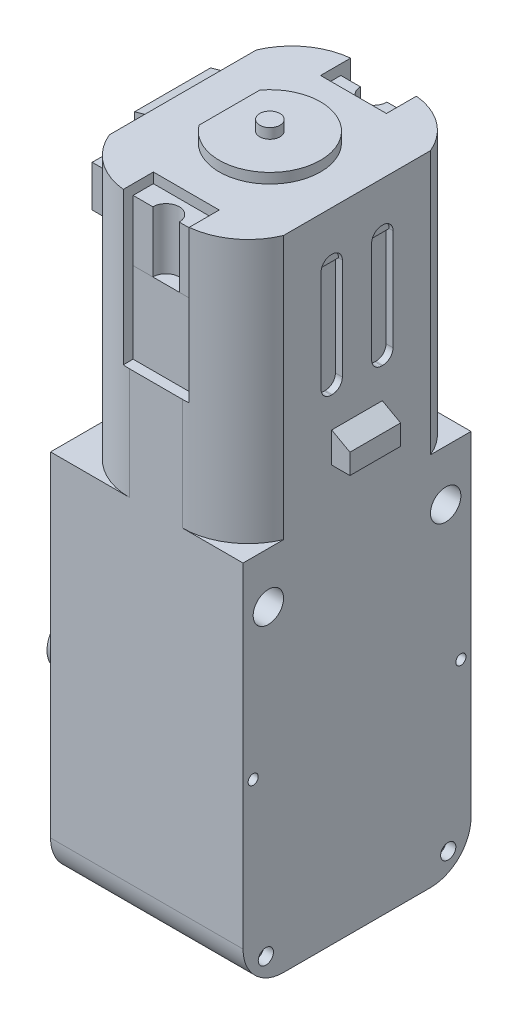
SolidWorks part; units mm, degrees
ref_plane "Alzado" through (0, 0, 0) normal (1, 0, 0) x (0, 1, 0)
ref_plane "Planta" through (0, 0, 0) normal (0, 0, 1) x (0, 1, 0)
ref_plane "Vista lateral" through (0, 0, 0) normal (0, 1, 0) x (-1, 0, 0)
sketch "Croquis1" plane through (0, 0, 0) normal (1, 0, 0) x (0, 1, 0)
  line L1 (-4.84, 11.25) -> (29.66, 11.25)
  line L2 (-7.34, 8.75) -> (-7.34, -8.75)
  line L3 (-4.84, -11.25) -> (29.66, -11.25)
  line L4 (29.66, 11.25) -> (29.66, -11.25)
  line L6 (5.66, 10.25) -> (-4.84, -8.75)
  line L8 (-4.84, 8.75) -> (5.66, -10.25)
  line L9 (-4.84, 0) -> (-0.0045, 0)
  arc A0 (-4.84, -11.25) -> (-7.34, -8.75) centre (-4.84, -8.75) cw
  arc A1 (-4.84, 11.25) -> (-7.34, 8.75) centre (-4.84, 8.75) ccw
  circle A2 centre (5.66, -10.25) radius 0.5
  circle A3 centre (5.66, 10.25) radius 0.5
  circle A4 centre (-0.0045, 0) radius 2.7322
  point P6 (-7.34, -11.25)
  point P9 (-7.34, 11.25)
  point P10 (-7.34, 0)
  dimension "D2" = 2.5
  dimension "D5" = 1
  dimension "D1" = 22.5
  dimension "D3" = 37
  dimension "D8" = 2.5
extrude "Saliente-Extruir2" add sketch "Croquis1" along normal blind 9.5 and the other way blind 9.5 contours L1 A1 L2 A0 L3 L4 A4 A2 A3 | A3 | L9 A4 L6 | L6 A4 L8 | L8 A4 L6 | L6 A4 L8 | L8 A4 L9 | A2 region at (0, 11.5559, 0) region at (0, 5.9069, -9.8315) region at (0, 1.4911, 0) region at (0, -0.0045, 1.745) region at (0, 5.4131, 10.6685) region at (0, -0.0045, -1.745) region at (0, -1.5001, 0.8823) region at (0, -1.5001, -0.8823)
sketch "Croquis2" plane through (0, 0, 0) normal (1, 0, 0) x (0, 1, 0)
  line L0 (-11.84, 3.2804) -> (-10.84, 3.2804)
  line L1 (-7.34, 8.75) -> (-7.34, -8.75) construction
  line L2 (-11.84, -2.5) -> (-11.84, 2.5)
  line L3 (-11.84, 0) -> (-13.0585, 0)
  line L4 (-11.84, -2.5) -> (-7.34, -2.5)
  line L5 (-11.84, -2.5) -> (-11.84, 2.5)
  line L6 (-11.84, 2.5) -> (-7.34, 2.5)
  line L7 (-7.34, -2.5) -> (-7.34, 2.5)
  line L8 (-11.84, -1.34) -> (-11.84, 1.34)
  line L10 (-12.4811, -2.5) -> (-12.4811, -1.5)
  line L11 (-12.4811, 2.5) -> (-12.4811, 1.5)
  circle A0 centre (-9.34, 0) radius 1.5
  dimension "D3" = 1
  dimension "D4" = 4.5
  dimension "D1" = 1
  dimension "D2" = 1
  dimension "D5" = 5
extrude "Saliente-Extruir4" add sketch "Croquis2" along normal blind 1.3 and the other way blind 1.3 contours L4 L7 L6 L5 L2 A0 region at (0, -11.7727, -1.92)
sketch "Croquis3" plane through (-9.5, 0, 0) normal (-1, 0, 0) x (0, -1, 0)
  circle A0 centre (0, 0) radius 2.5
extrude "Cortar-Extruir1" cut sketch "Croquis3" against normal blind 5
sketch "Croquis4" plane through (-9.5, 0, 0) normal (-1, 0, 0) x (0, 0, 1)
  line L0 (-12.6785, 24.66) -> (-12.6785, 5.66)
  line L2 (-11.25, 25.9631) -> (-10.25, 25.9631)
  line L3 (0, -7.34) -> (0, -15.1717)
  line L4 (8.75, -7.34) -> (-8.75, -7.34) construction
  line L5 (11.25, 25.9631) -> (10.25, 25.9631)
  line L6 (10.25, 25.9631) -> (10.25, 5.66)
  line L8 (-10.25, 4.4941) -> (-10.25, 25.9631)
  circle A0 centre (9.75, 5.66) radius 0.5
  circle A1 centre (8.75, -4.84) radius 0.75
  circle A2 centre (-9.75, 5.66) radius 0.5
  circle A3 centre (-8.75, -4.84) radius 0.75
  circle A4 centre (8.75, -4.84) radius 0.75
  circle A5 centre (9.75, 5.66) radius 0.5
  circle A6 centre (-9.75, 5.66) radius 0.5
  circle A7 centre (-8.75, -4.84) radius 0.75
  circle A8 centre (-8.75, -4.84) radius 0.75
  dimension "D3" = 1
  dimension "D4" = 1.5
  dimension "D1" = 19
  dimension "D2" = 1
sketch "Croquis5" plane through (9.5, 0, 0) normal (1, 0, 0) x (0, 1, 0)
  circle A0 centre (-4.84, 8.75) radius 0.75
  circle A1 centre (5.66, 9.75) radius 0.5
  circle A2 centre (5.66, -9.75) radius 0.5
  circle A3 centre (-4.84, -8.75) radius 0.75
extrude "Cortar-Extruir2" cut sketch "Croquis5" against normal blind 1
extrude "Cortar-Extruir3" cut sketch "Croquis4" against normal blind 1 contours A0 | A1 | A3 | A2 region at (-9.5, 5.66, 9.75) region at (-9.5, -4.84, 8.75) region at (-9.5, -4.84, -8.75)
sketch "Croquis6" plane through (-9.5, 0, 0) normal (-1, 0, 0) x (0, 0, 1)
  line L0 (13.1737, 24.66) -> (13.1737, 10.66)
  circle A0 centre (0, 10.66) radius 2
  dimension "D2" = 4
  dimension "D1" = 14
extrude "Saliente-Extruir6" add sketch "Croquis6" along normal blind 2 contours A0 region at (-9.5, 10.66, 0)
sketch "Croquis7" plane through (-9.5, 0, 0) normal (-1, 0, 0) x (0, 0, 1)
  line L0 (-11.25, 26.5829) -> (-10.25, 26.5829)
  line L1 (-12.8476, 24.66) -> (-12.8476, 19.66)
  line L2 (-10.25, 26.5829) -> (-10.25, 19.66)
  line L3 (-10.25, 19.66) -> (-12.8476, 19.66)
  line L4 (0, -11.84) -> (0, -18.0156)
  line L5 (-2.5, -11.84) -> (2.5, -11.84) construction
  line L7 (-7.25, 19.66) -> (-7.25, 21.16)
  line L8 (-7.25, 21.16) -> (-11.25, 21.16)
  circle A0 centre (-8.75, 19.66) radius 1.5
  circle A1 centre (8.75, 19.66) radius 1.5
  dimension "D1" = 1
  dimension "D2" = 5
  dimension "D3" = 1.5
  dimension "D4" = 4
extrude "Cortar-Extruir4" cut sketch "Croquis7" against normal through all contours A0 | A1 region at (-9.5, 19.66, -8.75)
sketch "Croquis8" plane through (0, 29.66, 0) normal (0, 1, 0) x (-1, 0, 0)
  line L1 (-3.5, 11.25) -> (1.7, 11.25)
  line L2 (-9.5, 7.25) -> (-9.5, -7.25)
  line L3 (-3.5, -11.25) -> (1.7, -11.25)
  line L4 (7.7, 7.25) -> (7.7, -7.25)
  line L5 (11.5, 0) -> (15.9145, 0)
  line L7 (11.5, -2) -> (11.5, 2) construction
  line L8 (0, 0) -> (0, 0.7272)
  arc A2 (7.7, 7.25) -> (1.7, 11.25) centre (1.7, 4.75) ccw
  arc A3 (7.7, -7.25) -> (1.7, -11.25) centre (1.7, -4.75) cw
  arc A5 (-3.5, 11.25) -> (-9.5, 7.25) centre (-3.5, 4.75) ccw
  arc A11 (-3.5, -11.25) -> (-9.5, -7.25) centre (-3.5, -4.75) cw
extrude "Saliente-Extruir7" add sketch "Croquis8" along normal blind 26 contours A11 A3 L4 A2 A5 region at (0.9, 29.66, 0)
sketch "Croquis9" plane through (-9.5, 0, 0) normal (-1, 0, 0) x (0, -1, 0)
  line L3 (-8.66, 15.3575) -> (-8.66, -16.1606) construction
  line L4 (-8.66, 15.3575) -> (18.8238, 15.3575)
  line L5 (-8.66, 15.3575) -> (-8.66, -16.1606)
  line L6 (-8.66, -16.1606) -> (18.8238, -16.1606)
  line L7 (18.8238, 15.3575) -> (18.8238, -16.1606)
extrude "Cortar-Extruir5" cut sketch "Croquis9" against normal through all
sketch "Croquis10" plane through (0, 8.66, 0) normal (0, -1, 0) x (-1, 0, 0)
  line L0 (9.5, -11.25) -> (9.5, 11.25) construction
  line L1 (9.5, -11.25) -> (-9.5, -11.25)
  line L2 (9.5, -11.25) -> (9.5, 11.25)
  line L3 (9.5, 11.25) -> (-9.5, 11.25)
  line L4 (-9.5, -11.25) -> (-9.5, 11.25)
  line L5 (0, 12.375) -> (0, -12.375) construction
  line L6 (-9.5, -11.25) -> (-9.5, -7.25) construction
  line L7 (-9.5, -11.25) -> (-9.5, 11.25) construction
  line L8 (9.5, -11.25) -> (1.7, -11.25) construction
  line L9 (9.5, -11.25) -> (-9.5, -11.25) construction
sketch "Croquis11" plane through (-9.5, 0, 0) normal (-1, 0, 0) x (0, 0, 1)
  line L1 (13.3634, 18.0947) -> (-15.0337, 18.0947)
  line L2 (13.3634, 18.0947) -> (13.3634, 2.7979)
  line L3 (13.3634, 2.7979) -> (-15.0337, 2.7979)
  line L4 (-15.0337, 18.0947) -> (-15.0337, 2.7979)
extrude "Cortar-Extruir7" cut sketch "Croquis11" against normal through all and the other way through all
sketch "Croquis12" plane through (-9.5, 0, 0) normal (-1, 0, 0) x (0, 0, 1)
  line L0 (-11.25, 29.66) -> (-11.25, 22.66)
  line L1 (-11.25, 18.0947) -> (-11.25, 29.66) construction
  line L3 (-11.25, 22.66) -> (12.1047, 22.66)
  line L4 (-11.25, 22.66) -> (-11.25, 15.491)
  line L5 (-11.25, 15.491) -> (12.1047, 15.491)
  line L6 (12.1047, 22.66) -> (12.1047, 15.491)
  line M2 (-11.25, 29.66) -> (-11.25, 18.0947)
  line M3 (-11.25, 18.0947) -> (11.25, 18.0947)
  line M4 (11.25, 18.0947) -> (11.25, 29.66)
  circle M6 centre (8.75, 19.66) radius 1.5
  circle M7 centre (-8.75, 19.66) radius 1.5
  dimension "D1" = 7
extrude "Cortar-Extruir8" cut sketch "Croquis12" against normal through all contours L3 M2 M3 M4 M6 M7 | L6 L3 L4 L5 M4 M3 region at (-9.5, 20.4918, 0) region at (-9.5, 17.009, 1.1057)
sketch "Croquis14" plane through (0, 22.66, 0) normal (0, -1, 0) x (-1, 0, 0)
  line L1 (9.5, -11.25) -> (-9.5, -11.25)
  line L2 (9.5, -11.25) -> (9.5, 11.25)
  line L3 (9.5, 11.25) -> (-9.5, 11.25)
  line L4 (-9.5, -11.25) -> (-9.5, 11.25)
extrude "Saliente-Extruir9" add sketch "Croquis14" along normal blind 30
sketch "Croquis15" plane through (-9.5, 0, 0) normal (-1, 0, 0) x (0, 0, 1)
  line L0 (0, -7.34) -> (0, -12.8155)
  line L1 (11.25, -7.34) -> (-11.25, -7.34) construction
  line L2 (-11.25, 29.66) -> (-10.25, 29.66)
  line L3 (-7.25, 29.66) -> (-11.25, 29.66) construction
  line L4 (-11.25, 29.66) -> (-11.25, 24.66)
  line L5 (-11.25, -7.34) -> (-11.25, 29.66) construction
  line L6 (-11.25, 24.66) -> (-10.25, 24.66)
  line L7 (-10.25, 24.66) -> (-10.25, 29.66)
  circle A0 centre (-8.75, 24.66) radius 1.5
  circle A1 centre (8.75, 24.66) radius 1.5
  dimension "D3" = 3
  dimension "D1" = 5
  dimension "D2" = 1
extrude "Cortar-Extruir9" cut sketch "Croquis15" against normal through all contours A1 | A0 region at (-9.5, 24.66, -8.75) region at (-9.5, 24.66, 8.75)
sketch "Croquis16" plane through (-9.5, 0, 0) normal (-1, 0, 0) x (0, 0, 1)
  line L0 (11.25, 29.66) -> (11.25, 15.66)
  line L1 (11.25, -7.34) -> (11.25, 29.66) construction
  circle A0 centre (0, 15.66) radius 2
  dimension "D2" = 4
  dimension "D1" = 14
extrude "Saliente-Extruir10" add sketch "Croquis16" along normal blind 2 contours A0 region at (-9.5, 15.66, 0)
sketch "Croquis17" plane through (-9.5, 0, 0) normal (-1, 0, 0) x (0, 0, 1)
  line L0 (11.25, 29.66) -> (11.25, 10.66)
  line L1 (11.25, -7.34) -> (11.25, 29.66) construction
  line L2 (11.25, 10.66) -> (10.75, 10.66)
  line L3 (11.25, -7.34) -> (-11.25, -7.34) construction
  line L4 (14.7504, -3.34) -> (14.7504, -7.34)
  line L5 (9.75, 10.66) -> (9.75, -12.757)
  line L6 (11.25, -3.34) -> (-13.714, -3.34)
  line L7 (11.25, -7.34) -> (7.25, -3.34)
  line L8 (0, -7.34) -> (0, -17.085)
  line L9 (-11.25, -3.34) -> (-11.25, -7.34)
  line L10 (-11.25, -7.34) -> (-7.25, -7.34)
  line L11 (-7.25, -7.34) -> (7.25, -7.34)
  line L12 (7.25, -7.34) -> (11.25, -7.34)
  line L13 (11.25, -3.34) -> (11.25, -7.34)
  line L14 (11.25, -7.34) -> (7.25, -7.34)
  line L15 (11.25, -3.34) -> (11.25, -7.34)
  circle A0 centre (10.25, 10.66) radius 0.5
  arc A1 (7.25, -7.34) -> (9.75, -0.2175) centre (7.25, -3.34) ccw
  circle A4 centre (9, -5.09) radius 0.75
  circle A5 centre (-9, -5.09) radius 0.75
  arc A6 (-7.25, -7.34) -> (-11.25, -3.34) centre (-7.25, -3.34) cw
  circle A7 centre (-10.25, 10.66) radius 0.5
  arc A8 (7.25, -7.34) -> (11.25, -3.34) centre (7.25, -3.34) ccw
  dimension "D3" = 1
  dimension "D4" = 8
  dimension "D5" = 1.5
  dimension "D1" = 19
  dimension "D2" = 0.5
sketch "Croquis18" plane through (-9.5, 0, 0) normal (-1, 0, 0) x (0, 0, 1)
extrude "Cortar-Extruir10" cut sketch "Croquis17" against normal through all contours A0 | A4 L7 | L7 A4 | A7 | A5 region at (-9.5, 10.66, 10.25) region at (-9.5, -4.8649, 9.2251) region at (-9.5, -5.3151, 8.7749) region at (-9.5, 10.66, -10.25)
sketch "Croquis19" plane through (-9.5, 0, 0) normal (-1, 0, 0) x (0, 0, 1)
  line L0 (11.25, -7.34) -> (11.25, -3.34)
  line L1 (11.25, -7.34) -> (11.25, 29.66) construction
  line L2 (0, -7.34) -> (0, -13.8514)
  line L3 (11.25, -7.34) -> (7.25, -7.34)
  line L4 (11.25, -7.34) -> (-11.25, -7.34) construction
  line L5 (-11.25, -7.34) -> (-7.25, -7.34)
  line L6 (-11.25, -7.34) -> (-11.25, -3.34)
  arc A0 (7.25, -7.34) -> (11.25, -3.34) centre (7.25, -3.34) ccw
  arc A1 (-7.25, -7.34) -> (-11.25, -3.34) centre (-7.25, -3.34) cw
  line M9 (-11.25, 29.66) -> (-11.25, -7.34)
  line M10 (-11.25, -7.34) -> (11.25, -7.34)
  line M11 (11.25, -7.34) -> (11.25, 29.66)
  dimension "D1" = 8
sketch "Croquis20" plane through (0, -7.34, 0) normal (0, -1, 0) x (1, 0, 0)
  line L5 (-8.6868, 10.6536) -> (8.5298, 10.6536)
  line L6 (-8.6868, 10.6536) -> (-8.6868, -10.8334)
  line L7 (-8.6868, -10.8334) -> (8.5298, -10.8334)
  line L8 (8.5298, 10.6536) -> (8.5298, -10.8334)
  line L9 (2.0429, 4.3316) -> (2.816, 4.3316)
  line L10 (2.0429, 4.3316) -> (2.0429, 4.8022)
  line L11 (2.0429, 4.8022) -> (2.816, 4.8022)
  line L12 (2.816, 4.3316) -> (2.816, 4.8022)
extrude "Saliente-Extruir12" add sketch "Croquis20" against normal blind 24 contours L10 L9 L12 L11
sketch "Croquis21" plane through (0, -7.34, 0) normal (0, -1, 0) x (-1, 0, 0)
  line L0 (9.5, -11.25) -> (-9.5, -11.25) construction
  line L1 (8.3272, -11.25) -> (-8.5298, -11.25)
  line L2 (8.3272, -11.25) -> (8.3272, 11.25)
  line L3 (8.3272, 11.25) -> (-8.5298, 11.25)
  line L4 (-8.5298, -11.25) -> (-8.5298, 11.25)
  line L5 (9.5, 11.25) -> (-9.5, 11.25) construction
extrude "Saliente-Extruir13" add sketch "Croquis21" against normal blind 24
extrude "Cortar-Extruir11" cut sketch "Croquis19" against normal through all contours A0 M10 M11 | A1 M10 M9 region at (-9.5, -6.4465, 10.3565) region at (-9.5, -6.4465, -10.3565)
sketch "Croquis22" plane through (-9.5, 0, 0) normal (-1, 0, 0) x (0, 0, 1)
  line L0 (7.25, -7.34) -> (17.3359, -7.34)
  line L1 (11.25, -7.34) -> (11.25, 3.86)
  line L2 (11.25, -3.34) -> (11.25, 29.66) construction
  line L3 (11.25, 3.86) -> (-11.25, 3.86)
  line L4 (-11.25, -3.34) -> (-11.25, 29.66) construction
  circle A0 centre (0, 3.86) radius 2.6
  dimension "D2" = 5.2
  dimension "D1" = 11.2
extrude "Cortar-Extruir12" cut sketch "Croquis22" against normal blind 5 contours L3 A0 | L3 A0 region at (-9.5, 2.7565, 0) region at (-9.5, 4.9635, 0)
sketch "Croquis23" plane through (-9.5, 0, 0) normal (-1, 0, 0) x (0, 0, 1)
  circle A0 centre (0, 3.86) radius 2.6
  circle A1 centre (0, 3.86) radius 2.75
  dimension "D1" = 5.5
extrude "Saliente-Extruir14" add sketch "Croquis23" along normal blind 0.5 draft 8 contours A1 | A0
sketch "Croquis24" plane through (0, -7.34, 0) normal (0, -1, 0) x (1, 0, 0)
  line L1 (-1.25, -2.5) -> (1.25, -2.5)
  line L2 (-1.25, -2.5) -> (-1.25, 2.5)
  line L3 (-1.25, 2.5) -> (1.25, 2.5)
  line L4 (1.25, -2.5) -> (1.25, 2.5)
  line L5 (-1.25, -2.5) -> (1.25, 2.5) construction
  line L6 (-1.25, 2.5) -> (1.25, -2.5) construction
  point P0 (0, 0)
  dimension "D1" = 2.5
  dimension "D2" = 5
extrude "Saliente-Extruir15" add sketch "Croquis24" along normal blind 4.7
sketch "Croquis25" plane through (-1.25, 0, 0) normal (-1, 0, 0) x (0, 0, 1)
  line L0 (2.5, -12.04) -> (-2.5, -12.04) construction
  circle A0 centre (0, -9.64) radius 1.4
  dimension "D1" = 2.8
  dimension "D2" = 2.4
extrude "Cortar-Extruir13" cut sketch "Croquis25" against normal blind 4.7
sketch "Croquis26" plane through (-7.7, 0, 0) normal (-1, 0, 0) x (0, -1, 0)
  line L0 (-29.66, -7.25) -> (-33.66, -7.25)
  line L1 (-55.66, -7.25) -> (-29.66, -7.25) construction
  line L2 (-33.66, -7.25) -> (-33.66, 7.25)
  line L3 (-55.66, 7.25) -> (-29.66, 7.25) construction
  line L5 (-36.66, 2.5) -> (-33.66, 2.5)
  line L6 (-36.66, 2.5) -> (-36.66, -2.5)
  line L7 (-36.66, -2.5) -> (-33.66, -2.5)
  line L8 (-33.66, 2.5) -> (-33.66, -2.5)
  line L9 (-36.66, 2.5) -> (-33.66, -2.5) construction
  line L10 (-36.66, -2.5) -> (-33.66, 2.5) construction
  point P5 (-35.16, 0)
  point P14 (-33.66, 0)
  dimension "D1" = 4
  dimension "D2" = 3
  dimension "D3" = 5
extrude "Saliente-Extruir17" add sketch "Croquis26" along normal blind 2 and the other way blind 19 contours L6 L7 L2 L5 region at (-7.7, 35.16, 0)
sketch "Croquis27" plane through (0, 0, 0) normal (0, 0, 1) x (0, 1, 0)
  line L0 (33.66, 9.7) -> (35.66, 9.7)
  line L1 (36.66, 9.7) -> (33.66, 9.7) construction
  line L2 (35.66, 9.7) -> (35.66, -11.3)
  line L3 (36.66, -11.3) -> (33.66, -11.3) construction
  line L4 (35.66, 9.7) -> (36.66, 7.7)
  line L5 (36.66, 7.7) -> (36.66, 9.7)
  line L6 (36.66, 9.7) -> (35.66, 9.7)
  line L7 (35.66, -11.3) -> (36.66, -9.5)
  line L8 (36.66, -9.5) -> (36.66, -11.3)
  line L9 (36.66, -11.3) -> (35.66, -11.3)
  dimension "D1" = 2
extrude "Cortar-Extruir14" cut sketch "Croquis27" against normal through all and the other way through all contours L5 L6 L4 | L9 L8 L7 region at (10.7, 36.3267, 0) region at (-9.0333, 36.3267, 0)
sketch "Croquis28" plane through (-7.7, 0, 0) normal (-1, 0, 0) x (0, -1, 0)
  line L0 (-36.66, -2.5) -> (-39.66, -2.5)
  line L1 (-36.66, 0) -> (-38.0942, 0)
  line L2 (-45.66, -1.4465) -> (-40.66, -1.4465)
  line L3 (-46.66, -2.4465) -> (-46.66, -2.5535)
  line L4 (-45.66, -3.5535) -> (-40.66, -3.5535)
  line L5 (-39.66, -2.4465) -> (-39.66, -2.5535)
  line L6 (-46.66, -1.4465) -> (-39.66, -3.5535) construction
  line L7 (-46.66, -3.5535) -> (-39.66, -1.4465) construction
  line L8 (-36.66, 2.5) -> (-36.66, -2.5) construction
  line L9 (-45.66, 3.5535) -> (-40.66, 3.5535)
  line L10 (-39.66, 2.4465) -> (-39.66, 2.5535)
  line L11 (-45.66, 1.4465) -> (-40.66, 1.4465)
  line L12 (-46.66, 2.4465) -> (-46.66, 2.5535)
  arc A0 (-45.66, -3.5535) -> (-46.66, -2.5535) centre (-45.66, -2.5535) cw
  arc A1 (-46.66, -2.4465) -> (-45.66, -1.4465) centre (-45.66, -2.4465) cw
  arc A2 (-39.66, -2.5535) -> (-40.66, -3.5535) centre (-40.66, -2.5535) cw
  arc A3 (-39.66, -2.4465) -> (-40.66, -1.4465) centre (-40.66, -2.4465) ccw
  arc A4 (-39.66, 2.5535) -> (-40.66, 3.5535) centre (-40.66, 2.5535) ccw
  arc A5 (-39.66, 2.4465) -> (-40.66, 1.4465) centre (-40.66, 2.4465) cw
  arc A6 (-45.66, 3.5535) -> (-46.66, 2.5535) centre (-45.66, 2.5535) ccw
  arc A7 (-46.66, 2.4465) -> (-45.66, 1.4465) centre (-45.66, 2.4465) ccw
  point P2 (-43.16, -2.5)
  dimension "D3" = 1
  dimension "D1" = 3
  dimension "D2" = 7
extrude "Cortar-Extruir15" cut sketch "Croquis28" against normal through all contours L12 A7 L11 A5 L10 A4 L9 A6 | L2 A3 L5 A2 L4 A0 L3 A1 region at (-7.7, 43.16, 2.5)
sketch "Croquis29" plane through (9.5, 0, 0) normal (1, 0, 0) x (0, 1, 0)
  line L0 (40.66, -1.4465) -> (45.66, -1.4465) construction
  line L5 (36.66, 0) -> (38.1303, 0)
  line L6 (36.66, -2.5) -> (36.66, 2.5) construction
  line L7 (40.66, -3.5535) -> (45.66, -3.5535) construction
  line L8 (40.66, -1.4465) -> (50.66, -1.4465)
  line L13 (40.66, -1.4465) -> (40.66, -3.5535)
  line L14 (40.66, -3.5535) -> (50.66, -3.5535)
  line L15 (51.66, -2.4465) -> (51.66, -2.5535)
  line L16 (40.66, 3.5535) -> (50.66, 3.5535)
  line L17 (51.66, 2.4465) -> (51.66, 2.5535)
  line L18 (40.66, 1.4465) -> (50.66, 1.4465)
  line L19 (40.66, 1.4465) -> (40.66, 3.5535)
  arc A1 (51.8241, -1.5254) -> (51.8281, -1.6145) centre (52.8241, -1.5254) ccw
  arc A2 (51.66, -2.5535) -> (50.66, -3.5535) centre (50.66, -2.5535) cw
  arc A3 (51.66, -2.4465) -> (50.66, -1.4465) centre (50.66, -2.4465) ccw
  arc A4 (51.66, 2.5535) -> (50.66, 3.5535) centre (50.66, 2.5535) ccw
  arc A5 (51.66, 2.4465) -> (50.66, 1.4465) centre (50.66, 2.4465) cw
  point P16 (52.66, -3.4465)
  point P19 (51.66, -3.5535)
  point P24 (39.66, -1.4465)
  arc M37 (45.66, -1.4465) -> (46.66, -2.4465) centre (45.66, -2.4465) cw
  line M38 (46.66, -2.4465) -> (46.66, -2.5535)
  arc M39 (46.66, -2.5535) -> (45.66, -3.5535) centre (45.66, -2.5535) cw
  arc M44 (45.66, 3.5535) -> (46.66, 2.5535) centre (45.66, 2.5535) cw
  line M45 (46.66, 2.5535) -> (46.66, 2.4465)
  arc M46 (46.66, 2.4465) -> (45.66, 1.4465) centre (45.66, 2.4465) cw
  dimension "D2" = 1
  dimension "D1" = 11
extrude "Cortar-Extruir16" cut sketch "Croquis29" against normal blind 7 contours A5 L17 A4 L16 L18 M44 M45 M46 | L15 A3 L8 L14 A2 M37 M38 M39 region at (9.5, 48.9563, -2.5) region at (9.5, 48.9563, 2.5)
sketch "Croquis30" plane through (0, 0, 0) normal (0, 0, 1) x (0, 1, 0)
  line L0 (55.66, 8.7) -> (48.16, 8.7)
  line L1 (55.66, 8.7) -> (55.66, 7.7)
  line L2 (55.66, 7.7) -> (55.66, 6.2)
  line L3 (55.66, 1.7) -> (55.66, 7.7) construction
  line L4 (55.66, 8.7) -> (55.66, 9.8676)
  line L5 (48.16, 8.7) -> (55.66, 8.7)
  line L6 (48.16, 8.7) -> (48.16, 7.7)
  line L7 (48.16, 7.7) -> (55.66, 7.7)
  line L8 (55.66, 8.7) -> (55.66, 7.7)
  line L9 (55.66, 9.8676) -> (54.66, 9.8676)
  line L10 (48.16, 8.7) -> (48.16, 10.3949)
  line L11 (48.16, 10.3949) -> (49.16, 10.3949)
  line L12 (49.16, 10.3949) -> (49.16, 7.7)
  line L13 (54.66, 9.8676) -> (54.66, 7.7)
  dimension "D1" = 7.5
  dimension "D2" = 1.5
  dimension "D3" = 1
  dimension "D4" = 1
  dimension "D5" = 1
extrude "Saliente-Extruir18" add sketch "Croquis30" along normal blind 3.75 and the other way blind 3.75 contours L6 L5 L8 L7
sketch "Croquis31" plane through (0, 0, 0) normal (0, 0, 1) x (0, 1, 0)
  line L0 (55.66, 8.7) -> (55.66, 9.5141)
  line L1 (55.66, 9.5141) -> (54.66, 9.5141)
  line L2 (48.16, 8.9893) -> (49.16, 8.9893)
  line L3 (49.16, 8.9893) -> (49.16, 7.7)
  line L4 (55.66, 7.7) -> (29.66, 7.7) construction
  line L5 (49.16, 7.7) -> (54.66, 7.7)
  line L7 (49.16, 7.7) -> (54.66, 7.7)
  line L8 (49.16, 7.7) -> (49.16, 6.2)
  line L9 (49.16, 6.2) -> (54.66, 6.2)
  line L10 (54.66, 7.7) -> (54.66, 6.2)
  dimension "D1" = 1
  dimension "D2" = 1
  dimension "D3" = 1.5
extrude "Cortar-Extruir17" cut sketch "Croquis31" against normal through all and the other way through all contours L10 L5 L8 L9 region at (-6.95, 51.91, 0)
sketch "Croquis32" plane through (0, 0, 0) normal (0, 0, 1) x (0, 1, 0)
  line L0 (48.16, 7.7) -> (48.16, 8.7)
  line L1 (48.16, 8.7) -> (48.926, 8.7)
  line L2 (48.16, 8.7) -> (55.66, 8.7) construction
  line L3 (48.926, 8.7) -> (48.16, 7.7)
extrude "Cortar-Extruir18" cut sketch "Croquis32" against normal through all and the other way through all
sketch "Croquis33" plane through (0, 0, 3.75) normal (0, 0, 1) x (1, 0, 0)
  line L0 (-7.7, 55.66) -> (-8.7, 55.3867)
  line L1 (-8.7, 48.926) -> (-8.7, 55.66) construction
  line L2 (-8.7, 55.3867) -> (-7.7, 55.3867)
  line L3 (-7.7, 55.66) -> (-7.7, 54.66) construction
  line L4 (-7.7, 55.3867) -> (-7.7, 55.66)
  line L5 (-8.7, 55.3867) -> (-8.7, 55.66)
  line L6 (-8.7, 55.66) -> (-7.7, 55.66)
  line L7 (-8.7, 55.3867) -> (-8.7, 55.66)
  line M4 (-8.7, 55.66) -> (-8.7, 48.926)
  line M9 (-7.7, 55.66) -> (-8.7, 55.66)
extrude "Cortar-Extruir22" cut sketch "Croquis33" against normal through all and the other way through all contours L0 M9 M4 region at (-8.3667, 55.5689, 3.75)
sketch "Croquis34" plane through (0, 55.66, 0) normal (0, 1, 0) x (1, 0, 0)
  line L5 (3.5, -11.25) -> (-1.7, -11.25)
  line L6 (0.9, -11.25) -> (0.9, -13.2757)
  line L7 (12.6416, 0) -> (17.759, 0)
  line L8 (4.15, -8.25) -> (-2.35, -8.25)
  line L9 (4.15, -8.25) -> (4.15, -11.25)
  line L10 (4.15, -11.25) -> (-2.35, -11.25)
  line L11 (-2.35, -8.25) -> (-2.35, -11.25)
  line L12 (4.15, -8.25) -> (-2.35, -11.25) construction
  line L13 (4.15, -11.25) -> (-2.35, -8.25) construction
  line L14 (4.15, 11.25) -> (-2.35, 11.25)
  line L15 (-2.35, 8.25) -> (-2.35, 11.25)
  line L16 (4.15, 8.25) -> (-2.35, 8.25)
  line L17 (4.15, 8.25) -> (4.15, 11.25)
  point P4 (0.9, -9.75)
  arc M9 (-7.7, -7.25) -> (-1.7, -11.25) centre (-1.7, -4.75) ccw
  line M10 (-1.7, -11.25) -> (3.5, -11.25)
  arc M11 (3.5, -11.25) -> (9.5, -7.25) centre (3.5, -4.75) ccw
  arc M13 (9.5, 7.25) -> (3.5, 11.25) centre (3.5, 4.75) ccw
  line M14 (3.5, 11.25) -> (-1.7, 11.25)
  arc M15 (-1.7, 11.25) -> (-7.7, 7.25) centre (-1.7, 4.75) ccw
  dimension "D1" = 6.5
  dimension "D2" = 3
extrude "Cortar-Extruir23" cut sketch "Croquis34" against normal blind 15 contours L8 L11 L5 L9 M9 M10 M11 | L16 L17 L15 M13 M14 M15 region at (0.9, 55.66, 9.7489) region at (0.9, 55.66, -9.7489)
sketch "Croquis35" plane through (0, 55.66, 0) normal (0, 1, 0) x (-1, 0, 0)
  line L0 (-9.5, 0) -> (3.1, 0)
  line L1 (-9.5, 11.25) -> (-9.5, -11.25) construction
  line L2 (7.7, -3.75) -> (7.7, 3.75) construction
  line L3 (-9.5, 7.25) -> (7.7, 7.25)
  line L4 (-5.9, 0) -> (3.1, 0)
  line L5 (3.1, 0) -> (3.1, 3)
  line L6 (3.1, 3) -> (3.1, -3)
  line L7 (4.1, 0) -> (7.7, 0)
  arc A0 (3.1, 3) -> (3.1, -3) centre (-0.9, 0) ccw
  dimension "D1" = 10
  dimension "D2" = 9
extrude "Cortar-Extruir24" cut sketch "Croquis35" against normal blind 5 contours L5 A0 L0 | L0 A0 L6 region at (1.1418, 55.66, 2.1759) region at (1.1418, 55.66, -2.1759)
sketch "Croquis37" plane through (0, 39.66, 0) normal (0, 1, 0) x (1, 0, 0)
  line L5 (8.8118, -6.8201) -> (-6.9662, -6.8201)
  line L6 (8.8118, -6.8201) -> (8.8118, 7.9883)
  line L7 (8.8118, 7.9883) -> (-6.9662, 7.9883)
  line L8 (-6.9662, -6.8201) -> (-6.9662, 7.9883)
extrude "Saliente-Extruir19" add sketch "Croquis37" along normal blind 11 separate body
sketch "Croquis38" plane through (-6.2, 0, 0) normal (-1, 0, 0) x (0, 0, 1)
  line L0 (-9.4404, 54.66) -> (-9.4404, 49.16) construction
  line L1 (9.4404, 54.66) -> (-9.4404, 54.66)
  line L2 (9.4404, 54.66) -> (9.4404, 50.5786)
  line L3 (9.4404, 50.5786) -> (-9.4404, 50.5786)
  line L4 (-9.4404, 54.66) -> (-9.4404, 50.5786)
extrude "Saliente-Extruir21" add sketch "Croquis38" along normal blind 1 separate body
sketch "Croquis39" plane through (-7.2, 0, 0) normal (-1, 0, 0) x (0, 0, 1)
  line L0 (3.75, 54.66) -> (7.25, 54.66) construction
  line L1 (4.5442, 54.66) -> (-4.5793, 54.66)
  line L2 (4.5442, 54.66) -> (4.5442, 50.5786)
  line L3 (4.5442, 50.5786) -> (-4.5793, 50.5786)
  line L4 (-4.5793, 54.66) -> (-4.5793, 50.5786)
  line L5 (-9.4404, 50.5786) -> (9.4404, 50.5786) construction
extrude "Saliente-Extruir23" add sketch "Croquis39" along normal blind 0.6 separate body
sketch "Croquis40" plane through (0, 40.66, 0) normal (0, 1, 0) x (-1, 0, 0)
  line L0 (2.35, -8.25) -> (2.35, -11.2174) construction
  line L1 (-4.15, -8.25) -> (2.35, -8.25)
  line L2 (-4.15, -8.25) -> (-4.15, -10.25)
  line L3 (-4.15, -10.25) -> (2.35, -10.25)
  line L4 (2.35, -8.25) -> (2.35, -10.25)
  line L5 (-11.3, 0) -> (-17.9203, 0)
  line L6 (-11.3, 2.5) -> (-11.3, -2.5) construction
  line L7 (-4.15, 10.25) -> (2.35, 10.25)
  line L8 (2.35, 8.25) -> (2.35, 10.25)
  line L9 (-4.15, 8.25) -> (2.35, 8.25)
  line L10 (-4.15, 8.25) -> (-4.15, 10.25)
  line M10 (2.35, -8.25) -> (-4.15, -8.25)
  line M11 (-4.15, -8.25) -> (-4.15, -11.2174)
  line M15 (2.35, -11.2174) -> (2.35, -8.25)
  dimension "D1" = 2
extrude "Saliente-Extruir24" add sketch "Croquis40" along normal blind 8 separate body contours L10 L9 L8 L7 | L3 M11 M15 M10 region at (0.9, 40.66, -9.25) region at (0.9, 40.66, 9.25)
sketch "Croquis41" plane through (0, 50.66, 0) normal (0, 1, 0) x (1, 0, 0)
  circle A0 centre (0.9, 0) radius 1
  dimension "D1" = 2
extrude "Saliente-Extruir26" add sketch "Croquis41" along normal blind 7 separate body contours A0
sketch "Croquis42" plane through (0, 48.66, 0) normal (0, 1, 0) x (1, 0, 0)
  line L0 (4.15, -10.25) -> (-2.35, -10.25) construction
  line L1 (-2.35, -8.25) -> (4.15, -8.25)
  line L2 (-2.35, -8.25) -> (-2.35, -10.25)
  line L3 (-2.35, -10.25) -> (-0.4059, -10.25)
  line L4 (4.15, -8.25) -> (4.15, -10.25)
  line L5 (2.2059, -10.25) -> (4.15, -10.25)
  line L6 (-11.5, 0) -> (-14.0238, 0)
  line L7 (-11.5, 2) -> (-11.5, -2) construction
  line L8 (2.2059, 10.25) -> (4.15, 10.25)
  line L9 (4.15, 8.25) -> (4.15, 10.25)
  line L10 (-2.35, 8.25) -> (4.15, 8.25)
  line L11 (-2.35, 8.25) -> (-2.35, 10.25)
  line L12 (-2.35, 10.25) -> (-0.4059, 10.25)
  arc A0 (2.2059, -10.25) -> (-0.4059, -10.25) centre (0.9, -10.25) ccw
  arc A1 (2.2059, 10.25) -> (-0.4059, 10.25) centre (0.9, 10.25) cw
  line M8 (4.15, -10.25) -> (4.15, -8.25)
  line M9 (4.15, -8.25) -> (-2.35, -8.25)
  line M10 (-2.35, -8.25) -> (-2.35, -10.25)
  line M11 (-2.35, -10.25) -> (4.15, -10.25)
extrude "Saliente-Extruir27" add sketch "Croquis42" along normal blind 6 separate body contours A0 M11 M8 M9 M10 | L8 A1 L12 L11 L10 L9 region at (0.9, 48.66, 8.318) region at (3.1779, 48.66, -10.182)
sketch "Croquis43" plane through (0, 50.66, 0) normal (0, 1, 0) x (1, 0, 0)
  line L0 (-3.1, -3) -> (-3.1, 3)
  arc A0 (-3.1, -3) -> (-3.1, 3) centre (0.9, 0) ccw
extrude "Saliente-Extruir28" add sketch "Croquis43" along normal blind 6 separate body contours A0 L0
sketch "Croquis44" plane through (0, 50.66, 0) normal (0, 1, 0) x (1, 0, 0)
  line L1 (9.1152, -4.8548) -> (3.9007, -4.8548)
  line L2 (9.1152, -4.8548) -> (9.1152, 4.72)
  line L3 (9.1152, 4.72) -> (3.9007, 4.72)
  line L4 (3.9007, -4.8548) -> (3.9007, 4.72)
extrude "Saliente-Extruir29" add sketch "Croquis44" along normal blind 2 separate body
sketch "Croquis46" plane through (-7.2, 0, 0) normal (-1, 0, 0) x (0, 0, 1)
  line L0 (4.5442, 50.5786) -> (4.5442, 54.66) construction
  line L4 (8.1975, 52.779) -> (8.1975, 52.4596)
  line L5 (0, 57.66) -> (0, 63.4537)
  line L6 (1, 57.66) -> (-1, 57.66) construction
  line L7 (-8.1975, 52.779) -> (-8.1975, 52.4596)
  line L12 (-4.5442, 53.779) -> (-7.1975, 53.779)
  line L13 (-4.5442, 51.4596) -> (-4.5442, 53.779)
  line L14 (4.5442, 51.4596) -> (7.1975, 51.4596)
  line L15 (4.5442, 51.4596) -> (4.5442, 53.779)
  line L16 (4.5442, 53.779) -> (7.1975, 53.779)
  line L17 (8.1975, 51.4596) -> (8.1975, 53.779)
  line L18 (-4.5442, 51.4596) -> (-7.1975, 51.4596)
  arc A0 (7.1975, 51.4596) -> (8.1975, 52.4596) centre (7.1975, 52.4596) ccw
  arc A1 (7.1975, 53.779) -> (8.1975, 52.779) centre (7.1975, 52.779) cw
  circle A2 centre (7.1975, 52.6193) radius 0.6976
  circle A3 centre (-7.1975, 52.6193) radius 0.6976
  arc A4 (-7.1975, 51.4596) -> (-8.1975, 52.4596) centre (-7.1975, 52.4596) cw
  arc A5 (-7.1975, 53.779) -> (-8.1975, 52.779) centre (-7.1975, 52.779) ccw
  point P0 (4.5442, 52.6193)
  point P9 (4.5442, 53.779)
  dimension "D1" = 1
extrude "Saliente-Extruir32" add sketch "Croquis46" along normal blind 0.4 separate body contours A1 L16 L15 L14 A0 L4 A2 | L12 A5 L7 A4 L18 L13 A3 region at (-7.2, 52.6193, 6.0712) region at (-7.2, 52.6193, -6.0712)
sketch "Croquis47" plane through (-4.5, 0, 0) normal (-1, 0, 0) x (0, 0, 1)
  circle A0 centre (0, 3.86) radius 2.6
  dimension "D1" = 5.2
extrude "Saliente-Extruir33" add sketch "Croquis47" along normal blind 14 separate body
sketch "Croquis48" plane through (-18.5, 0, 0) normal (-1, 0, 0) x (0, 0, 1)
  line L0 (0, 5.61) -> (2.9802, 5.61)
  line L1 (2.9802, 5.61) -> (-2.9064, 5.61)
  line L2 (-2.9064, 5.61) -> (0, 2.11)
  line L3 (0, 2.11) -> (3.1399, 2.11)
  line L4 (3.1399, 2.11) -> (-3.086, 2.11)
  circle A0 centre (0, 3.86) radius 2.6
  circle A1 centre (0, 3.86) radius 1.75
  circle M3 centre (0, 3.86) radius 2.6
  dimension "D1" = 3.5
extrude "Cortar-Extruir25" cut sketch "Croquis48" against normal blind 8 contours L1 L0 M3 | L3 L4 M3 region at (-18.5, 5.9553, 0) region at (-18.5, 1.7647, 0)
sketch "Croquis49" plane through (-18.5, 0, 0) normal (-1, 0, 0) x (0, 0, 1)
  circle A0 centre (0, 3.86) radius 1
extrude "Cortar-Extruir26" cut sketch "Croquis49" against normal blind 8
